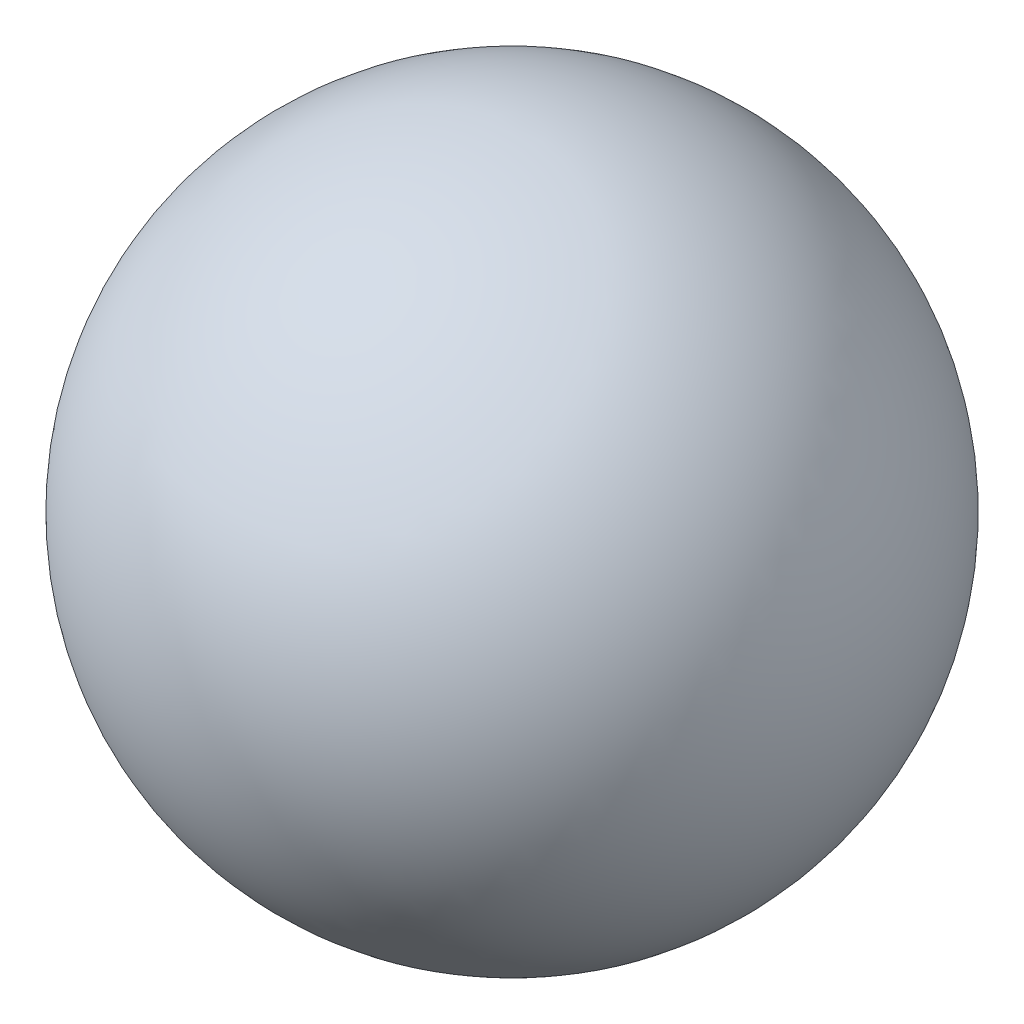
SolidWorks part; units mm, degrees
material "非常高密度 PE (SS)"
ref_plane "前视基准面" through (0, 0, 0) normal (0, 0, 1) x (1, 0, 0)
ref_plane "上视基准面" through (0, 0, 0) normal (0, 1, 0) x (1, 0, 0)
ref_plane "右视基准面" through (0, 0, 0) normal (1, 0, 0) x (0, 0, -1)
sketch "草图1" plane through (0, 0, 0) normal (0, 0, 1) x (1, 0, 0)
  line L0 (0, 27.1796) -> (0, -33.9565) construction
  line L1 (0, 21) -> (0, -21)
  arc A0 (0, -21) -> (0, 21) centre (0, 0) ccw
  dimension "D1" = 42
revolve "旋转6" add sketch "草图1" angle 360 about L0
